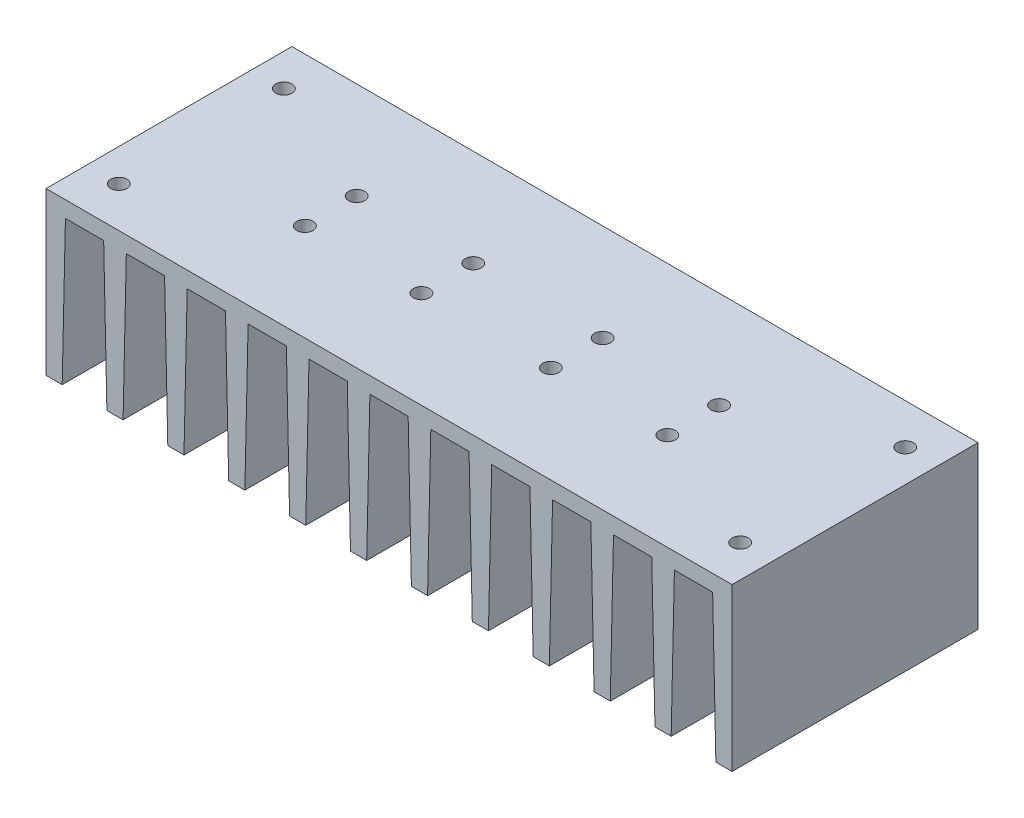
SolidWorks part; units mm, degrees
ref_plane "Front Plane" through (0, 0, 0) normal (0, 0, 1) x (1, 0, 0)
ref_plane "Top Plane" through (0, 0, 0) normal (0, 1, 0) x (1, 0, 0)
ref_plane "Right Plane" through (0, 0, 0) normal (1, 0, 0) x (0, 0, -1)
sketch "Sketch1" plane through (0, 0, 0) normal (0, 1, 0) x (1, 0, 0)
  line L1 (-106, -38) -> (106, -38)
  line L2 (-106, -38) -> (-106, 38)
  line L3 (-106, 38) -> (106, 38)
  line L4 (106, -38) -> (106, 38)
  line L5 (-106, -38) -> (106, 38) construction
  line L6 (-106, 38) -> (106, -38) construction
  point P0 (0, 0)
  dimension "D1" = 212
  dimension "D2" = 76
extrude "Boss-Extrude1" add sketch "Sketch1" along normal blind 50
sketch "Sketch2" plane through (0, 0, 38) normal (0, 0, 1) x (1, 0, 0)
  line L0 (101, 0) -> (100, 45)
  line L1 (-106, 0) -> (106, 0) construction
  line L2 (100, 45) -> (88.1818, 45)
  line L3 (88.1818, 45) -> (87.1818, 0)
  line L4 (68.3636, 0) -> (82.1818, 0)
  line L5 (87.1818, 0) -> (101, 0)
  line L6 (-106, 50) -> (106, 50) construction
  line L7 (82.1818, 0) -> (81.1818, 45)
  line L8 (81.1818, 45) -> (69.3636, 45)
  line L9 (69.3636, 45) -> (68.3636, 0)
  line L10 (49.5455, 0) -> (63.3636, 0)
  line L11 (63.3636, 0) -> (62.3636, 45)
  line L12 (62.3636, 45) -> (50.5455, 45)
  line L13 (50.5455, 45) -> (49.5455, 0)
  line L14 (30.7273, 0) -> (44.5455, 0)
  line L15 (44.5455, 0) -> (43.5455, 45)
  line L16 (43.5455, 45) -> (31.7273, 45)
  line L17 (31.7273, 45) -> (30.7273, 0)
  line L18 (11.9091, 0) -> (25.7273, 0)
  line L19 (25.7273, 0) -> (24.7273, 45)
  line L20 (24.7273, 45) -> (12.9091, 45)
  line L21 (12.9091, 45) -> (11.9091, 0)
  line L22 (-6.9091, 0) -> (6.9091, 0)
  line L23 (6.9091, 0) -> (5.9091, 45)
  line L24 (5.9091, 45) -> (-5.9091, 45)
  line L25 (-5.9091, 45) -> (-6.9091, 0)
  line L26 (-25.7273, 0) -> (-11.9091, 0)
  line L27 (-11.9091, 0) -> (-12.9091, 45)
  line L28 (-12.9091, 45) -> (-24.7273, 45)
  line L29 (-24.7273, 45) -> (-25.7273, 0)
  line L30 (-44.5454, 0) -> (-30.7273, 0)
  line L31 (-30.7273, 0) -> (-31.7273, 45)
  line L32 (-31.7273, 45) -> (-43.5454, 45)
  line L33 (-43.5454, 45) -> (-44.5454, 0)
  line L34 (-63.3636, 0) -> (-49.5454, 0)
  line L35 (-49.5454, 0) -> (-50.5454, 45)
  line L36 (-50.5454, 45) -> (-62.3636, 45)
  line L37 (-62.3636, 45) -> (-63.3636, 0)
  line L38 (-82.1818, 0) -> (-68.3636, 0)
  line L39 (-68.3636, 0) -> (-69.3636, 45)
  line L40 (-69.3636, 45) -> (-81.1818, 45)
  line L41 (-81.1818, 45) -> (-82.1818, 0)
  line L42 (-101, 0) -> (-87.1818, 0)
  line L43 (-87.1818, 0) -> (-88.1818, 45)
  line L44 (-88.1818, 45) -> (-100, 45)
  line L45 (-100, 45) -> (-101, 0)
  dimension "D1" = 5
  dimension "D2" = 13.8182
  dimension "D3" = 1
  dimension "D4" = 1
  dimension "D5" = 5
  dimension "D7" = 5
  dimension "D6" = 11
extrude "Cut-Extrude1" cut sketch "Sketch2" against normal blind 77
sketch "Sketch4" plane through (0, 50, 0) normal (0, 1, 0) x (1, 0, 0)
  line L0 (-27.5, 0) -> (27.5, 0) construction
  line L1 (0, -27.5) -> (0, 27.5) construction
  circle A0 centre (-96, 25.5) radius 2.5
  circle A1 centre (-96, -25.5) radius 2.5
  circle A2 centre (96, 25.5) radius 2.5
  circle A3 centre (96, -25.5) radius 2.5
  circle A4 centre (-56, 8) radius 2.5
  circle A5 centre (-20, 8) radius 2.5
  circle A7 centre (-20, -8) radius 2.5
  circle A8 centre (-56, -8) radius 2.5
  circle A9 centre (56, -8) radius 2.5
  circle A10 centre (20, -8) radius 2.5
  circle A11 centre (20, 8) radius 2.5
  circle A12 centre (56, 8) radius 2.5
  dimension "D1" = 96
  dimension "D5" = 5
  dimension "D6" = 5
  dimension "D7" = 96
  dimension "D11" = 5
  dimension "D12" = 5
  dimension "D13" = 20
  dimension "D16" = 5
  dimension "D17" = 5
  dimension "D2" = 96
  dimension "D3" = 25.5
  dimension "D4" = 25.5
  dimension "D8" = 25.5
  dimension "D9" = 25.5
  dimension "D10" = 96
  dimension "D14" = 56
  dimension "D15" = 8
extrude "Cut-Extrude2" cut sketch "Sketch4" against normal blind 77
